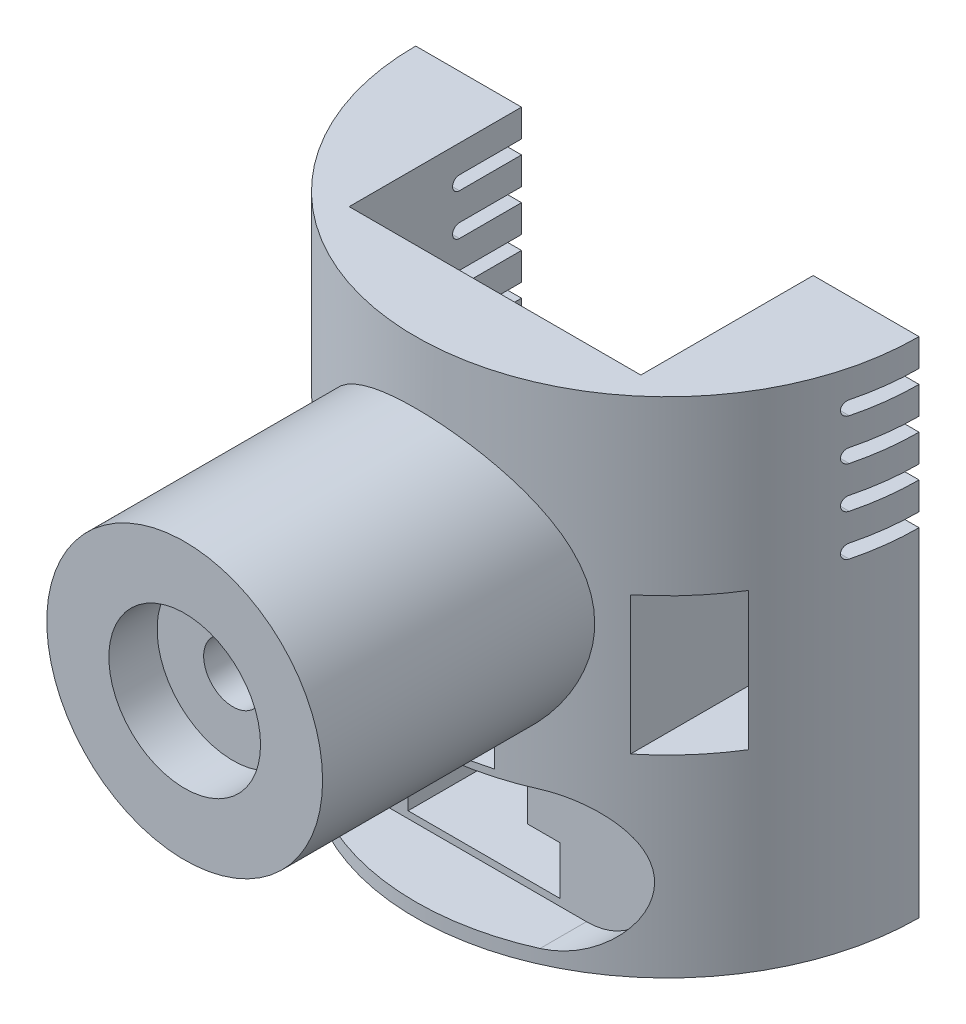
SolidWorks part; units mm, degrees
ref_plane "Front Plane" through (0, 0, 0) normal (0, 0, 1) x (1, 0, 0)
ref_plane "Top Plane" through (0, 0, 0) normal (0, 1, 0) x (1, 0, 0)
ref_plane "Right Plane" through (0, 0, 0) normal (1, 0, 0) x (0, 0, -1)
sketch "Sketch1" plane through (0, 0, 0) normal (0, 1, 0) x (1, 0, 0)
  circle A0 centre (0, 0) radius 36.5
  dimension "D1" = 73
extrude "Boss-Extrude1" add sketch "Sketch1" along normal blind 3
sketch "Sketch2" plane through (0, 3, 0) normal (0, 1, 0) x (1, 0, 0)
  line L0 (-11, 0) -> (-11, -34.803)
  line L1 (11, 0) -> (11, -34.803)
  arc A0 (11, -34.803) -> (-11, -34.803) centre (0, 0) ccw
  arc A1 (11, 0) -> (-11, 0) centre (0, 0) ccw
  dimension "D1" = 73
  dimension "D2" = 11
extrude "Boss-Extrude2" add sketch "Sketch2" along normal blind 7
sketch "Sketch3" plane through (0, 3, 0) normal (0, 1, 0) x (1, 0, 0)
  circle A0 centre (0, 0) radius 4.15
  dimension "D1" = 8.3
extrude "Cut-Extrude1" cut sketch "Sketch3" against normal up to next
sketch "Sketch4" plane through (0, 10, 0) normal (0, 1, 0) x (1, 0, 0)
  line L1 (-6.35, -3.6662) -> (-6.35, -35.9434)
  line L3 (6.35, -3.6662) -> (6.35, 3.6662)
  line L4 (6.35, 3.6662) -> (0, 7.3323)
  line L5 (0, 7.3323) -> (-6.35, 3.6662)
  line L6 (-6.35, 3.6662) -> (-6.35, -3.6662)
  line L8 (6.35, -3.6662) -> (6.35, -35.9434)
  line L10 (-3.175, -5.4993) -> (-0.7775, -6.8834) [skipped]
  line L11 (3.175, -5.4993) -> (6.35, -3.6662) [skipped]
  arc A0 (6.35, -35.9434) -> (-6.35, -35.9434) centre (0, 0) ccw
  arc A1 (6.35, 0) -> (-6.35, 0) centre (0, 0) ccw construction
  arc A2 (6.35, -35.9434) -> (-6.35, -35.9434) centre (0, 0) ccw
  arc M3 (-11, 0) -> (11, 0) centre (0, 0) cw
  line M4 (11, 0) -> (11, -34.803)
  arc M5 (11, -34.803) -> (-11, -34.803) centre (0, 0) ccw
  line M6 (-11, -34.803) -> (-11, 0)
  dimension "D1" = 73
  dimension "D2" = 6.35
extrude "Boss-Extrude3" add sketch "Sketch4" along normal blind 8 contours M6 M3 M4 M5 | L8 A0 L1 L6 L5 L4 L3 M4 M3 M6 region at (-6.8684, 10, 19.8048) region at (0, 10, -35.4796)
sketch "Sketch5" plane through (0, 18, 0) normal (0, 1, 0) x (1, 0, 0)
  line L5 (0, 0) -> (24, 21.15) construction
  circle A0 centre (0, 0) radius 36.5
  dimension "D1" = 73
extrude "Boss-Extrude4" add sketch "Sketch5" along normal blind 5
sketch "Sketch6" plane through (0, 23, 0) normal (0, 1, 0) x (1, 0, 0)
  line L1 (-21.15, -25) -> (21.15, -25)
  line L2 (-21.15, -25) -> (-21.15, 25)
  line L3 (-21.15, 25) -> (21.15, 25)
  line L4 (21.15, -25) -> (21.15, 25)
  line L5 (-21.15, -25) -> (21.15, 25) construction
  line L6 (-21.15, 25) -> (21.15, -25) construction
  circle A0 centre (0, 0) radius 36.5
  dimension "D1" = 73
  dimension "D2" = 42.3
  dimension "D3" = 50
extrude "Boss-Extrude5" add sketch "Sketch6" along normal blind 50
ref_plane "Plane1" through (0, 0, 38.6) normal (0, 0, -1) x (-1, 0, 0)
sketch "Sketch7" plane through (0, 0, 38.6) normal (0, 0, -1) x (-1, 0, 0)
  line L0 (-36.5, 0) -> (36.5, 0) construction
  line L1 (-14.8667, 2) -> (14.8667, 2)
  line L3 (-14.8667, 22) -> (14.8667, 22)
  line L6 (-5.6045, 15.7698) -> (5.6045, 8.2302) construction
  line L7 (0, 12) -> (5.6045, 15.7698) construction
  arc A0 (-14.8667, 22) -> (-14.8667, 2) centre (-14.8667, 12) ccw
  arc A1 (14.8667, 2) -> (14.8667, 22) centre (14.8667, 12) ccw
  point P0 (0, 12)
  dimension "D1" = 12
  dimension "D2" = 20
extrude "Cut-Extrude3" cut sketch "Sketch7" along normal blind 12
sketch "Sketch9" plane through (0, 0, 0) normal (0, 0, 1) x (1, 0, 0)
  line L1 (0, 0) -> (54.5049, 0)
  line L2 (0, 0) -> (0, 78.124)
  line L3 (0, 78.124) -> (54.5049, 78.124)
  line L4 (54.5049, 0) -> (54.5049, 78.124)
ref_plane "Plane3" through (0, 0, 70) normal (0, 0, 1) x (1, 0, 0)
sketch "Sketch11" plane through (0, 0, 70) normal (0, 0, 1) x (1, 0, 0)
  line L0 (38.5, 0) -> (-38.5, 0) construction
  circle A0 centre (0, 44) radius 20
  dimension "D1" = 40
  dimension "D2" = 44
extrude "Boss-Extrude7" add sketch "Sketch11" against normal up to next
revolve "Cut-Revolve1" cut sketch "Sketch9" angle 180 about L2
ref_plane "Plane2" through (0, 0, 70) normal (0, 0, 1) x (1, 0, 0)
sketch "Sketch12" plane through (0, 0, 70) normal (0, 0, 1) x (1, 0, 0)
  circle A0 centre (0, 44) radius 11
  dimension "D1" = 22
extrude "Cut-Extrude4" cut sketch "Sketch12" against normal blind 7
sketch "Sketch13" plane through (0, 0, 63) normal (0, 0, 1) x (1, 0, 0)
  circle A0 centre (0, 44) radius 4.25
  dimension "D1" = 8.5
extrude "Cut-Extrude5" cut sketch "Sketch13" against normal up to next
sketch "Sketch14" plane through (0, 0, 25) normal (0, 0, -1) x (-1, 0, 0)
  circle A0 centre (0, 44) radius 11
  dimension "D1" = 22
extrude "Cut-Extrude6" cut sketch "Sketch14" against normal blind 31
ref_plane "Plane4" through (0, 0, 5) normal (0, 0, 1) x (1, 0, 0)
sketch "Sketch16" plane through (0, 0, 5) normal (0, 0, 1) x (1, 0, 0)
  line L0 (36.5, 73) -> (-36.5, 73) construction
  line L1 (-31, 48) -> (-23, 48)
  line L2 (-31, 48) -> (-31, 28)
  line L3 (-31, 28) -> (-23, 28)
  line L4 (-23, 48) -> (-23, 28)
  line L5 (23, 48) -> (31, 48)
  line L6 (23, 48) -> (23, 28)
  line L7 (23, 28) -> (31, 28)
  line L8 (31, 48) -> (31, 28)
  line L9 (0, -38.5) -> (0, 38.5) construction
  dimension "D1" = 20
  dimension "D2" = 8
  dimension "D3" = 25
  dimension "D4" = 23
  dimension "D5" = 23
  dimension "D6" = 8
  dimension "D7" = 20
  dimension "D8" = 25
extrude "Cut-Extrude7" cut sketch "Sketch16" along normal up to next
sketch "Sketch17" plane through (0, 0, 5) normal (0, 0, 1) x (1, 0, 0)
  line L0 (-23, 48) -> (-23, 28) construction
  line L1 (-31, 48) -> (-23, 48) construction
  line L2 (23, 28) -> (23, 48) construction
  line L3 (23, 48) -> (23, 28) construction
  line L4 (23, 48) -> (31, 48) construction
  line L5 (-23, 28) -> (-23, 48) construction
  circle A0 centre (27, 42) radius 1.375
  circle A1 centre (27, 34) radius 1.375
  circle A2 centre (-27, 42) radius 1.375
  circle A3 centre (-27, 34) radius 1.375
  point P8 (-69.3506, 83.8613)
  dimension "D4" = 2.75
  dimension "D5" = 2.75
  dimension "D6" = 2.75
  dimension "D7" = 2.75
  dimension "D1" = 4
  dimension "D2" = 6
  dimension "D3" = 8
  dimension "D8" = 4
  dimension "D9" = 8
  dimension "D10" = 4
  dimension "D11" = 6
  dimension "D12" = 4
extrude "Cut-Extrude8" cut sketch "Sketch17" against normal up to next
sketch "Sketch18" plane through (0, 0, 25) normal (0, 0, -1) x (-1, 0, 0)
  line L0 (21.15, 23) -> (-21.15, 23) construction
  line L1 (-10, 23) -> (10, 23)
  line L2 (-10, 23) -> (-10, 31.9)
  line L3 (-10, 31.9) -> (10, 31.9)
  line L4 (10, 23) -> (10, 31.9)
  line L5 (21.15, 73) -> (21.15, 23) construction
  point P8 (0, 31.9)
  dimension "D1" = 21.15
  dimension "D2" = 20
  dimension "D3" = 8.9
extrude "Cut-Extrude9" cut sketch "Sketch18" against normal blind 15
sketch "Sketch19" plane through (0, 0, 5) normal (0, 0, 1) x (1, 0, 0)
  line L1 (-23.94, 42) -> (-25.47, 44.65)
  line L2 (-25.47, 44.65) -> (-28.53, 44.65)
  line L3 (-28.53, 44.65) -> (-30.06, 42)
  line L4 (-30.06, 42) -> (-28.53, 39.35)
  line L5 (-28.53, 39.35) -> (-25.47, 39.35)
  line L6 (-25.47, 39.35) -> (-23.94, 42)
  line L7 (-23.94, 34) -> (-25.47, 36.65)
  line L8 (-25.47, 36.65) -> (-28.53, 36.65)
  line L9 (-28.53, 36.65) -> (-30.06, 34)
  line L10 (-30.06, 34) -> (-28.53, 31.35)
  line L11 (-28.53, 31.35) -> (-25.47, 31.35)
  line L12 (-25.47, 31.35) -> (-23.94, 34)
  line L13 (30.06, 42) -> (28.53, 44.65)
  line L14 (28.53, 44.65) -> (25.47, 44.65)
  line L15 (25.47, 44.65) -> (23.94, 42)
  line L16 (23.94, 42) -> (25.47, 39.35)
  line L17 (25.47, 39.35) -> (28.53, 39.35)
  line L18 (28.53, 39.35) -> (30.06, 42)
  line L19 (30.06, 34) -> (28.53, 36.65)
  line L20 (28.53, 36.65) -> (25.47, 36.65)
  line L21 (25.47, 36.65) -> (23.94, 34)
  line L22 (23.94, 34) -> (25.47, 31.35)
  line L23 (25.47, 31.35) -> (28.53, 31.35)
  line L24 (28.53, 31.35) -> (30.06, 34)
  circle A0 centre (-27, 42) radius 2.65 construction
  circle A1 centre (-27, 34) radius 2.65 construction
  circle A2 centre (27, 42) radius 2.65 construction
  circle A3 centre (27, 34) radius 2.65 construction
  dimension "D1" = 5.3
  dimension "D2" = 5.3
  dimension "D3" = 5.3
  dimension "D4" = 5.3
extrude "Cut-Extrude10" cut sketch "Sketch19" against normal blind 2.1
ref_plane "Plane5" through (36.5, 0, 0) normal (1, 0, 0) x (0, 0, -1)
sketch "Sketch20" plane through (36.5, 0, 0) normal (1, 0, 0) x (0, 0, -1)
  line L0 (0, 73) -> (-36.5, 73) construction
  line L1 (0, 69) -> (-10, 69)
  line L2 (0, 69) -> (0, 67)
  line L3 (0, 67) -> (-10, 67)
  line L4 (-10, 69) -> (-10, 67)
  line L5 (0, 63) -> (-10, 63)
  line L6 (0, 63) -> (0, 61)
  line L7 (0, 61) -> (-10, 61)
  line L8 (-10, 63) -> (-10, 61)
  line L9 (0, 40.15) -> (0, -40.15) construction
  line L10 (0, 57) -> (-10, 57)
  line L11 (0, 57) -> (0, 55)
  line L12 (0, 55) -> (-10, 55)
  line L13 (-10, 57) -> (-10, 55)
  line L14 (0, 51) -> (-10, 51)
  line L15 (0, 51) -> (0, 49)
  line L16 (0, 49) -> (-10, 49)
  line L17 (-10, 51) -> (-10, 49)
  dimension "D1" = 2
  dimension "D2" = 2
  dimension "D3" = 4
  dimension "D4" = 4
  dimension "D5" = 4
  dimension "D6" = 2
  dimension "D7" = 4
  dimension "D8" = 2
  dimension "D9" = 10
  dimension "D10" = 0
  dimension "D11" = 10
  dimension "D12" = 0
  dimension "D13" = 10
  dimension "D14" = 10
  dimension "D15" = 0
extrude "Cut-Extrude11" cut sketch "Sketch20" against normal through all
fillet "Fillet1" radius 1 16 edges at (-28.1267, 55, 10) (-28.1267, 61, 10) (-28.1267, 67, 10) (-28.1267, 69, 10) (-28.1267, 63, 10) (-28.1267, 57, 10) (-28.1267, 51, 10) (-28.1267, 49, 10) (28.1267, 51, 10) (28.1267, 49, 10) (28.1267, 55, 10) (28.1267, 57, 10) (28.1267, 63, 10) (28.1267, 61, 10) (28.1267, 69, 10) (28.1267, 67, 10)
